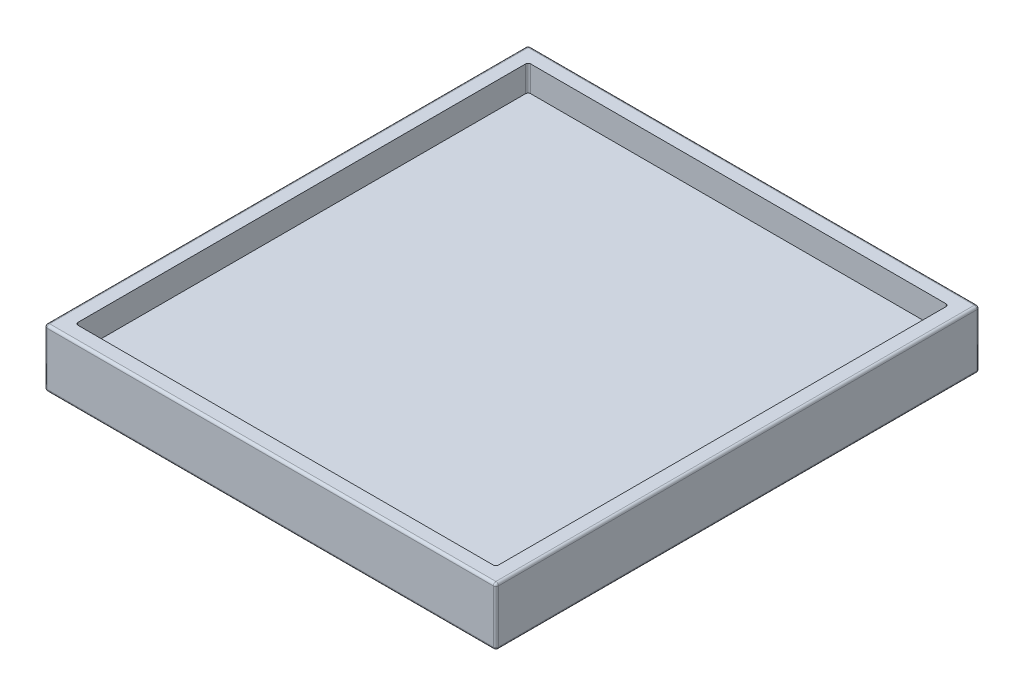
SolidWorks part; units mm, degrees
ref_plane "Front Plane" through (0, 0, 0) normal (0, 0, 1) x (1, 0, 0)
ref_plane "Top Plane" through (0, 0, 0) normal (0, 1, 0) x (1, 0, 0)
ref_plane "Right Plane" through (0, 0, 0) normal (1, 0, 0) x (0, 0, -1)
sketch "Sketch1" plane through (0, 0, 0) normal (0, 1, 0) x (1, 0, 0)
  line L1 (0, 0) -> (70, 0)
  line L2 (0, 0) -> (0, 75)
  line L3 (0, 75) -> (70, 75)
  line L4 (70, 0) -> (70, 75)
  dimension "D1" = 75
  dimension "D2" = 70
extrude "Boss-Extrude1" add sketch "Sketch1" along normal blind 9
sketch "Sketch2" plane through (0, 9, 0) normal (0, 1, 0) x (1, 0, 0)
  line L0 (35, 75) -> (35, 0) construction
  line L1 (70, 75) -> (0, 75) construction
  line L2 (0, 0) -> (70, 0) construction
  line L4 (2.4, 2.4) -> (67.6, 2.4)
  line L5 (2.4, 2.4) -> (2.4, 72.6)
  line L6 (2.4, 72.6) -> (67.6, 72.6)
  line L7 (67.6, 2.4) -> (67.6, 72.6)
  line L8 (2.4, 2.4) -> (67.6, 72.6) construction
  line L9 (2.4, 72.6) -> (67.6, 2.4) construction
  point P6 (35, 37.5)
  dimension "D1" = 70.2
  dimension "D2" = 65.2
extrude "Cut-Extrude1" cut sketch "Sketch2" against normal offset from surface (4 mm away) 5 up to face at (35, 0, -37.5)
sketch "Sketch4" plane through (0, 0, 0) normal (0, -1, 0) x (1, 0, 0)
  line L0 (35, 0) -> (35, -75) construction
  line L1 (0, 0) -> (70, 0) construction
  line L2 (70, -75) -> (0, -75) construction
  circle A0 centre (17.5, -54) radius 2.5
  circle A1 centre (52.5, -54) radius 2.5
  point P8 (0, 0)
  dimension "D1" = 5
  dimension "D2" = 35
  dimension "D3" = 54
extrude "Boss-Extrude3" add sketch "Sketch4" along normal blind 7.5
fillet "Fillet1" radius 0.4 20 edges at (2.4, 7, -2.4) (67.6, 7, -2.4) (67.6, 7, -72.6) (2.4, 7, -72.6) (35, 0, 0) (70, 0, -37.5) (35, 0, -75) (0, 9, -37.5) (35, 9, 0) (70, 9, -37.5) (35, 9, -75) (0, 0, -37.5) (0, 4.5, -75) (70, 4.5, -75) (70, 4.5, 0) (0, 4.5, 0) (52.5, 0, -51.5) (17.5, 0, -56.5) (52.5, -7.5, -51.5) (17.5, -7.5, -56.5)
